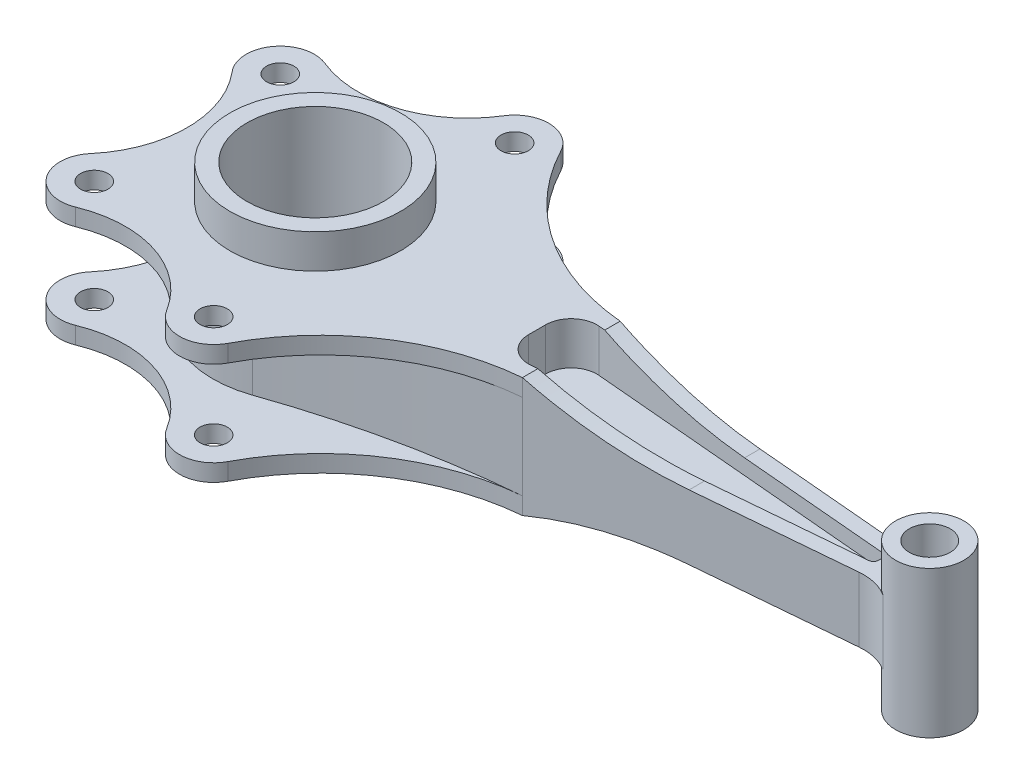
SolidWorks part; units mm, degrees
ref_plane "Front Plane" through (0, 0, 0) normal (0, 0, 1) x (1, 0, 0)
ref_plane "Top Plane" through (0, 0, 0) normal (0, 1, 0) x (1, 0, 0)
ref_plane "Right Plane" through (0, 0, 0) normal (1, 0, 0) x (0, 0, -1)
sketch "Sketch1" plane through (0, 0, 0) normal (0, 1, 0) x (1, 0, 0)
  line L0 (0, 0) -> (180, 0) construction
  line L1 (46.3525, 0) -> (14.3237, 44.0839) construction
  line L2 (14.3237, 44.0839) -> (-37.5, 27.2453) construction
  line L3 (-37.5, 27.2453) -> (-37.5, -27.2453) construction
  line L4 (-37.5, -27.2453) -> (14.3237, -44.0839) construction
  line L5 (14.3237, -44.0839) -> (46.3525, 0) construction
  line L6 (75, -14.3144) -> (171.8813, -5.8383)
  line L7 (75, 14.3144) -> (171.8813, 5.8383)
  circle A0 centre (0, 0) radius 25
  circle A1 centre (0, 0) radius 20
  circle A2 centre (0, 0) radius 37.5 construction
  arc A3 (23.1692, -48.7483) -> (75, -14.3144) centre (80.6651, -79.067) cw
  circle A4 centre (180, 0) radius 10
  circle A5 centre (180, 0) radius 6
  circle A6 centre (-37.5, -27.2453) radius 4
  circle A7 centre (14.3237, -44.0839) radius 4
  circle A8 centre (14.3237, 44.0839) radius 4
  circle A9 centre (-37.5, 27.2453) radius 4
  circle A10 centre (-37.5, -27.2453) radius 10
  circle A11 centre (14.3237, -44.0839) radius 10
  circle A12 centre (14.3237, 44.0839) radius 10
  circle A13 centre (-37.5, 27.2453) radius 10
  arc A14 (-45.1256, 20.7761) -> (-45.1256, -20.7761) centre (-69.6154, 0) cw
  arc A15 (-33.7039, 36.4968) -> (5.8147, 49.3372) centre (-21.5124, 66.2082) ccw
  arc A16 (-33.7039, -36.4968) -> (5.8147, -49.3372) centre (-21.5124, -66.2082) cw
  arc A17 (23.1692, 48.7483) -> (75, 14.3144) centre (80.6651, 79.067) ccw
  dimension "D1" = 8
  dimension "D2" = 20
  dimension "D3" = 75
  dimension "D4" = 50
  dimension "D5" = 5
  dimension "D7" = 12
  dimension "D8" = 20
  dimension "D11" = 65
  dimension "D6" = 180
  dimension "D9" = 5
  dimension "D10" = 75
extrude "Boss-Extrude1" add sketch "Sketch1" along normal mid plane 35 contours A17 A12 A15 A13 A14 A10 A16 A11 A3 L6 A4 L7 A0 | A12 A8 | A13 A9 | A10 A6 | A11 A7 | A0 A1 region at (46.6995, 0, 0) region at (14.6532, 0, 53.7955) region at (-45.3613, 0, 32.9569) region at (23.7563, 0, -46.4185) region at (-45.3613, 0, -32.9569) region at (-24.2929, 0, 0)
extrude "Boss-Extrude2" add sketch "Sketch1<4>" along normal mid plane 55 contours A0 A1 region at (-24.2929, 0, 0)
sketch "Sketch1<4>" plane through (0, 0, 0) normal (0, 1, 0) x (1, 0, 0) same geometry as "Sketch1"
sketch "Sketch2" plane through (0, 0, 0) normal (0, 1, 0) x (1, 0, 0)
  line L1 (0, 0) -> (75, 0) construction
  line L2 (75, -14.3144) -> (75, 14.3144) construction
  circle A0 centre (0, 0) radius 20 construction
  circle A1 centre (0, 0) radius 20
  arc A2 (9.906, 28.3173) -> (9.906, -28.3173) centre (0, 0) ccw
  arc A3 (9.906, -28.3173) -> (75, -14.3144) centre (98.3429, -281.1248) cw
  arc A4 (75, -14.3144) -> (23.1692, -48.7483) centre (80.6651, -79.067) ccw construction
  arc A5 (9.906, 28.3173) -> (75, 14.3144) centre (98.3429, 281.1248) ccw
  arc A6 (23.1692, 48.7483) -> (75, 14.3144) centre (80.6651, 79.067) ccw construction
  circle A7 centre (14.3237, 44.0839) radius 10 construction
  arc A8 (-33.7039, 36.4968) -> (5.8147, 49.3372) centre (-21.5124, 66.2082) ccw construction
  circle A9 centre (-37.5, 27.2453) radius 10 construction
  arc A10 (-45.1256, -20.7761) -> (-45.1256, 20.7761) centre (-69.6154, 0) ccw construction
  circle A11 centre (-37.5, -27.2453) radius 10 construction
  arc A12 (5.8147, -49.3372) -> (-33.7039, -36.4968) centre (-21.5124, -66.2082) ccw construction
  circle A13 centre (14.3237, -44.0839) radius 10 construction
  arc A14 (75, -14.3144) -> (23.1692, -48.7483) centre (80.6651, -79.067) ccw construction
  arc A15 (23.1692, 48.7483) -> (75, 14.3144) centre (80.6651, 79.067) ccw
  arc A16 (23.1692, 48.7483) -> (5.8147, 49.3372) centre (14.3237, 44.0839) ccw
  arc A17 (-33.7039, 36.4968) -> (5.8147, 49.3372) centre (-21.5124, 66.2082) ccw
  arc A18 (-33.7039, 36.4968) -> (-45.1256, 20.7761) centre (-37.5, 27.2453) ccw
  arc A19 (-45.1256, -20.7761) -> (-45.1256, 20.7761) centre (-69.6154, 0) ccw
  arc A20 (-45.1256, -20.7761) -> (-33.7039, -36.4968) centre (-37.5, -27.2453) ccw
  arc A21 (5.8147, -49.3372) -> (-33.7039, -36.4968) centre (-21.5124, -66.2082) ccw
  arc A22 (5.8147, -49.3372) -> (23.1692, -48.7483) centre (14.3237, -44.0839) ccw
  arc A23 (75, -14.3144) -> (23.1692, -48.7483) centre (80.6651, -79.067) ccw
  circle A24 centre (0, 0) radius 25 construction
  circle A25 centre (0, 0) radius 25 construction
  dimension "D1" = 5
extrude "Cut-Extrude1" cut sketch "Sketch2" against normal mid plane 25
sketch "Sketch3" plane through (0, 0, 0) normal (0, 0, 1) x (1, 0, 0)
  line L0 (171.8813, 17.5) -> (171.8813, -17.5) construction
  line L1 (171.8813, 17.5) -> (171.8813, 9.5)
  line L2 (75, 17.5) -> (23.1692, 17.5) construction
  line L3 (119.8999, 9.5) -> (171.8813, 9.5)
  line L4 (171.8813, 0) -> (75, 0) construction
  line L5 (75, -12.5) -> (75, 12.5) construction
  line L6 (75, 17.5) -> (171.8813, 17.5) construction
  line L7 (119.8999, 17.5) -> (171.8813, 17.5)
  line L8 (119.8999, 17.5) -> (75, 17.5)
  arc A0 (75, 17.5) -> (119.8999, 9.5) centre (119.8999, 139.5) ccw
  dimension "D2" = 130
  dimension "D1" = 8
extrude "Cut-Extrude2" cut sketch "Sketch3" against normal through all both and the other way through all
mirror "Mirror1" about plane through (0, 0, 0) normal (0, 1, 0) of "Cut-Extrude2"
extrude "Boss-Extrude3" add sketch "Sketch1<5>" along normal mid plane 43 contours A4 A5 region at (170.2828, 0, 0)
sketch "Sketch1<5>" plane through (0, 0, 0) normal (0, 1, 0) x (1, 0, 0) same geometry as "Sketch1"
fillet "Fillet3" radius 15 2 edges at (171.8813, 0, -5.8383) (171.8813, 0, 5.8383)
sketch "Sketch4" plane through (0, 17.5, 0) normal (0, 1, 0) x (1, 0, 0)
  line L2 (65, 10.6721) -> (65, -10.6721)
  line L3 (75, 14.3144) -> (75, -14.3144) construction
  line L4 (75, 14.3144) -> (75, -14.3144) construction
  line L10 (165.2554, 1.9009) -> (119.5077, 5.9033)
  line L11 (119.5077, 5.9033) -> (74.6078, 9.8315)
  line L12 (165.6209, 1.8689) -> (119.5077, 5.9033)
  line L13 (119.5077, 5.9033) -> (65, 10.6721)
  line L17 (165.2554, -1.9009) -> (119.5077, -5.9033)
  line L18 (119.5077, -5.9033) -> (74.6078, -9.8315)
  line L19 (165.6209, -1.8689) -> (119.5077, -5.9033)
  line L20 (119.5077, -5.9033) -> (65, -10.6721)
  arc A2 (172.4339, 12.3695) -> (172.4339, -12.3695) centre (180, 0) ccw
  arc A3 (165.6209, 1.8689) -> (165.6209, -1.8689) centre (180, 0) ccw
  dimension "D4" = 10
  dimension "D1" = 4.5
  dimension "D2" = 4.5
  dimension "D3" = 4.5
extrude "Cut-Extrude3" cut sketch "Sketch4" against normal blind 12.5
mirror "Mirror2" about plane through (0, 0, 0) normal (0, 1, 0) of "Cut-Extrude3"
fillet "Fillet1" radius 7.5 4 edges at (65, -11.25, 10.6721) (65, -11.25, -10.6721) (65, 11.25, 10.6721) (65, 11.25, -10.6721)
fillet "Fillet2" radius 1.5 4 edges at (165.6209, 7.25, 1.8689) (165.6209, 7.25, -1.8689) (165.6209, -7.25, -1.8689) (165.6209, -7.25, 1.8689)
